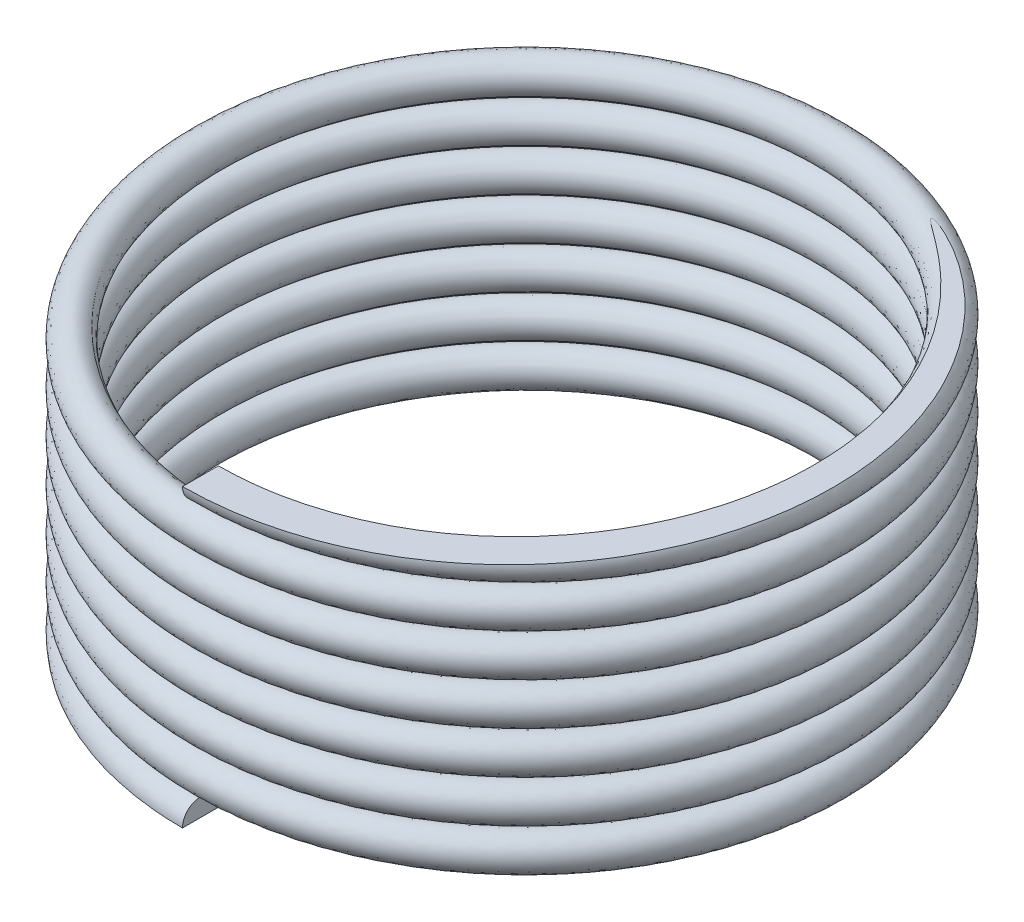
SolidWorks part; units mm, degrees
material "Stainless Steel (ferritic)"
ref_plane "Front Plane" through (0, 0, 0) normal (0, 0, 1) x (1, 0, 0)
ref_plane "Top Plane" through (0, 0, 0) normal (0, 1, 0) x (1, 0, 0)
ref_plane "Right Plane" through (0, 0, 0) normal (1, 0, 0) x (0, 0, -1)
sketch "Sketch1" plane through (0, 0, 0) normal (0, 1, 0) x (1, 0, 0)
  circle A0 centre (0, 0) radius 3.7465
  dimension "D1" = 7.493
curve "Helix/Spiral1" pitch 0.508 height 3.556 radius 3.7465 left hand yes centre (0, 0, 0) axis (0, 1, 0) start towards (0, 0, 1)
sketch "Sketch2" plane through (0, 0, 0) normal (1, 0, 0) x (0, 0, -1)
  circle A0 centre (-3.7465, 0) radius 0.2159
  spline S0 degree 3 poles (-3.7465, 0) (-3.7465, 0.0105) (-3.5514, 0.0318) (-2.7181, 0.0635) (-1.471, 0.0953) (0, 0.127) (1.471, 0.1588) (2.7181, 0.1905) (3.5514, 0.2223) (3.844, 0.254) (3.5514, 0.2858) (2.7181, 0.3175) (1.471, 0.3493) (0, 0.381) (-1.471, 0.4128) (-2.7181, 0.4445) (-3.5514, 0.4763) (-3.844, 0.508) (-3.5514, 0.5398) (-2.7181, 0.5715) (-1.471, 0.6033) (0, 0.635) (1.471, 0.6667) (2.7181, 0.6985) (3.5514, 0.7302) (3.844, 0.762) (3.5514, 0.7937) (2.7181, 0.8255) (1.471, 0.8572) (0, 0.889) (-1.471, 0.9207) (-2.7181, 0.9525) (-3.5514, 0.9842) (-3.844, 1.016) (-3.5514, 1.0477) (-2.7181, 1.0795) (-1.471, 1.1113) (0, 1.143) (1.471, 1.1747) (2.7181, 1.2065) (3.5514, 1.2383) (3.844, 1.27) (3.5514, 1.3018) (2.7181, 1.3335) (1.471, 1.3653) (0, 1.397) (-1.471, 1.4288) (-2.7181, 1.4605) (-3.5514, 1.4923) (-3.844, 1.524) (-3.5514, 1.5558) (-2.7181, 1.5875) (-1.471, 1.6193) (0, 1.651) (1.471, 1.6828) (2.7181, 1.7145) (3.5514, 1.7463) (3.844, 1.778) (3.5514, 1.8098) (2.7181, 1.8415) (1.471, 1.8733) (0, 1.905) (-1.471, 1.9368) (-2.7181, 1.9685) (-3.5514, 2.0003) (-3.844, 2.032) (-3.5514, 2.0638) (-2.7181, 2.0955) (-1.471, 2.1273) (0, 2.159) (1.471, 2.1908) (2.7181, 2.2225) (3.5514, 2.2543) (3.844, 2.286) (3.5514, 2.3178) (2.7181, 2.3495) (1.471, 2.3813) (0, 2.413) (-1.471, 2.4448) (-2.7181, 2.4765) (-3.5514, 2.5083) (-3.844, 2.54) (-3.5514, 2.5718) (-2.7181, 2.6035) (-1.471, 2.6353) (0, 2.667) (1.471, 2.6988) (2.7181, 2.7305) (3.5514, 2.7623) (3.844, 2.794) (3.5514, 2.8258) (2.7181, 2.8575) (1.471, 2.8893) (0, 2.921) (-1.471, 2.9528) (-2.7181, 2.9845) (-3.5514, 3.0162) (-3.844, 3.048) (-3.5514, 3.0797) (-2.7181, 3.1115) (-1.471, 3.1432) (0, 3.175) (1.471, 3.2067) (2.7181, 3.2385) (3.5514, 3.2702) (3.844, 3.302) (3.5514, 3.3337) (2.7181, 3.3655) (1.471, 3.3972) (0, 3.429) (-1.471, 3.4607) (-2.7181, 3.4925) (-3.5514, 3.5242) (-3.7465, 3.5455) (-3.7465, 3.556) knots 0 0 0 0 0.008929 0.017857 0.026786 0.035714 0.044643 0.053571 0.0625 0.071429 0.080357 0.089286 0.098214 0.107143 0.116071 0.125 0.133929 0.142857 0.151786 0.160714 0.169643 0.178571 0.1875 0.196429 0.205357 0.214286 0.223214 0.232143 0.241071 0.25 0.258929 0.267857 0.276786 0.285714 0.294643 0.303571 0.3125 0.321429 0.330357 0.339286 0.348214 0.357143 0.366071 0.375 0.383929 0.392857 0.401786 0.410714 0.419643 0.428571 0.4375 0.446429 0.455357 0.464286 0.473214 0.482143 0.491071 0.5 0.508929 0.517857 0.526786 0.535714 0.544643 0.553571 0.5625 0.571429 0.580357 0.589286 0.598214 0.607143 0.616071 0.625 0.633929 0.642857 0.651786 0.660714 0.669643 0.678571 0.6875 0.696429 0.705357 0.714286 0.723214 0.732143 0.741071 0.75 0.758929 0.767857 0.776786 0.785714 0.794643 0.803571 0.8125 0.821429 0.830357 0.839286 0.848214 0.857143 0.866071 0.875 0.883929 0.892857 0.901786 0.910714 0.919643 0.928571 0.9375 0.946429 0.955357 0.964286 0.973214 0.982143 0.991071 1 1 1 1 construction
  dimension "D1" = 0.4318
sweep "Sweep1" add profiles "Sketch2" path "Helix/Spiral1"
sketch "Sketch9" plane through (0, 0, 0) normal (0, 1, 0) x (1, 0, 0)
  circle A0 centre (0, 0.0879) radius 5.6877
extrude "Cut-Extrude1" cut sketch "Sketch9" against normal blind 2.54
ref_plane "Plane1" through (0, 3.556, 0) normal (0, 1, 0) x (1, 0, 0)
sketch "Sketch10" plane through (0, 3.556, 0) normal (0, 1, 0) x (1, 0, 0)
  circle A0 centre (0, 0) radius 5.0836
extrude "Cut-Extrude2" cut sketch "Sketch10" along normal blind 2.54
ref_axis "Axis1" through (0, 3.9713, 0) along (0, -1, 0)
